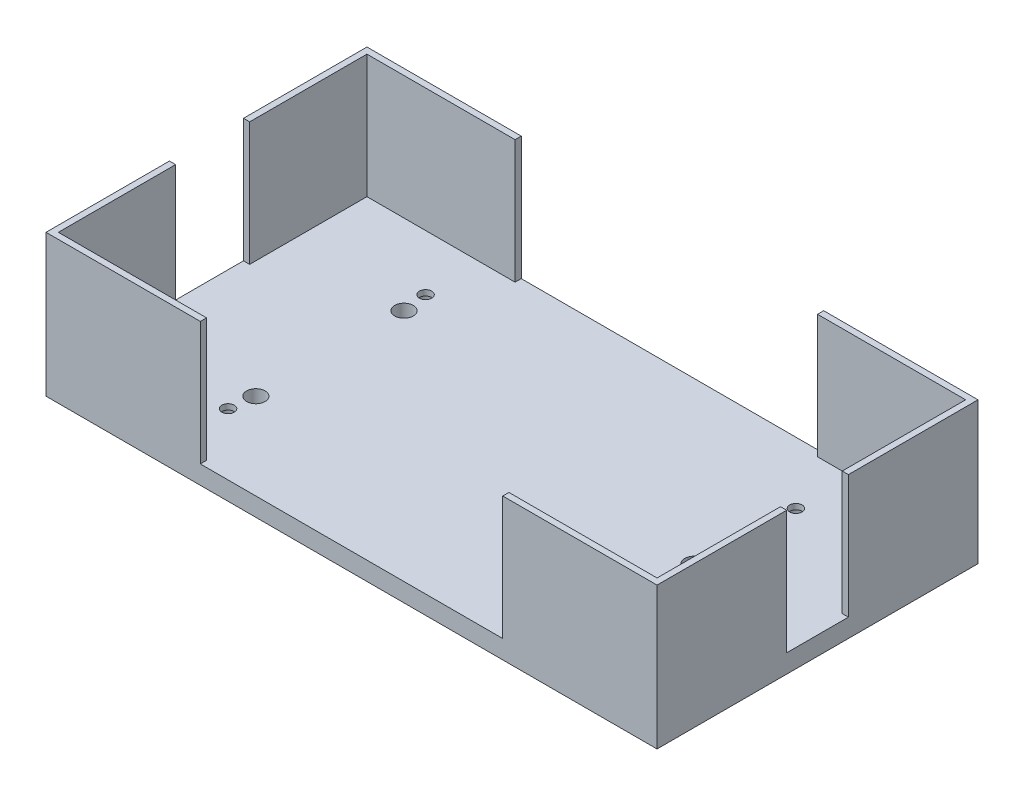
SolidWorks part; units mm, degrees
ref_plane "Front Plane" through (0, 0, 0) normal (0, 0, 1) x (1, 0, 0)
ref_plane "Top Plane" through (0, 0, 0) normal (0, 1, 0) x (1, 0, 0)
ref_plane "Right Plane" through (0, 0, 0) normal (1, 0, 0) x (0, 0, -1)
sketch "Sketch1" plane through (0, 0, 0) normal (0, 1, 0) x (1, 0, 0)
  line L1 (-60.2291, 12.7329) -> (38.7709, 12.7329)
  line L2 (-60.2291, 12.7329) -> (-60.2291, -39.2671)
  line L3 (-60.2291, -39.2671) -> (38.7709, -39.2671)
  line L4 (38.7709, 12.7329) -> (38.7709, -39.2671)
  dimension "D1" = 52
  dimension "D2" = 99
extrude "Boss-Extrude1" add sketch "Sketch1" along normal blind 3 contours L2 L1 L4 L3
sketch "Sketch5" plane through (0, 3, 0) normal (0, 1, 0) x (1, 0, 0)
  line L0 (-60.2291, 12.7329) -> (-60.2291, -39.2671) construction
  line L1 (-60.2291, -39.2671) -> (38.7709, -39.2671) construction
  line L3 (38.7709, 12.7329) -> (38.7709, -39.2671) construction
  circle A0 centre (-40.2291, -25.2671) radius 1.5
  circle A1 centre (-40.2291, -1.2671) radius 1.5
  circle A2 centre (18.7709, -13.2671) radius 1.5
  dimension "D1" = 3
  dimension "D2" = 3
  dimension "D3" = 3
  dimension "D4" = 20
  dimension "D5" = 14
  dimension "D6" = 20
  dimension "D7" = 24
  dimension "D8" = 26
  dimension "D9" = 20
extrude "Cut-Extrude3" cut sketch "Sketch5" against normal through all
sketch "Sketch6" plane through (0, 3, 0) normal (0, 1, 0) x (1, 0, 0)
  line L0 (-60.2291, 12.7329) -> (-60.2291, -39.2671) construction
  line L1 (-60.2291, -38.2671) -> (-59.2291, -38.2671)
  line L2 (-60.2291, -38.2671) -> (-60.2291, -19.2671)
  line L3 (-60.2291, -19.2671) -> (-59.2291, -19.2671)
  line L4 (-59.2291, -38.2671) -> (-59.2291, -19.2671)
  line L5 (-60.2291, -39.2671) -> (38.7709, -39.2671) construction
  line L6 (-60.2291, -7.2671) -> (-59.2291, -7.2671)
  line L7 (-60.2291, -7.2671) -> (-60.2291, 11.7329)
  line L8 (-60.2291, 11.7329) -> (-59.2291, 11.7329)
  line L9 (-59.2291, -7.2671) -> (-59.2291, 11.7329)
  line L10 (-60.2291, 12.7329) -> (38.7709, 12.7329) construction
  line L11 (38.7709, 12.7329) -> (38.7709, -39.2671) construction
  line L12 (37.7709, -38.2671) -> (38.7709, -38.2671)
  line L13 (37.7709, -38.2671) -> (37.7709, -18.2671)
  line L14 (37.7709, -18.2671) -> (38.7709, -18.2671)
  line L15 (38.7709, -38.2671) -> (38.7709, -18.2671)
  line L17 (37.7709, -8.2671) -> (38.7709, -8.2671)
  line L18 (37.7709, -8.2671) -> (37.7709, 11.7329)
  line L19 (37.7709, 11.7329) -> (38.7709, 11.7329)
  line L20 (38.7709, -8.2671) -> (38.7709, 11.7329)
  line L21 (-60.2291, -39.2671) -> (-35.2291, -39.2671)
  line L22 (-60.2291, -39.2671) -> (-60.2291, -38.2671)
  line L23 (-60.2291, -38.2671) -> (-35.2291, -38.2671)
  line L24 (-35.2291, -39.2671) -> (-35.2291, -38.2671)
  line L25 (13.7709, -39.2671) -> (38.7709, -39.2671)
  line L26 (13.7709, -39.2671) -> (13.7709, -38.2671)
  line L27 (13.7709, -38.2671) -> (38.7709, -38.2671)
  line L28 (38.7709, -39.2671) -> (38.7709, -38.2671)
  line L29 (-60.2291, 11.7329) -> (-35.2291, 11.7329)
  line L30 (-60.2291, 11.7329) -> (-60.2291, 12.7329)
  line L31 (-60.2291, 12.7329) -> (-35.2291, 12.7329)
  line L32 (-35.2291, 11.7329) -> (-35.2291, 12.7329)
  line L33 (13.7709, 11.7329) -> (38.7709, 11.7329)
  line L34 (13.7709, 11.7329) -> (13.7709, 12.7329)
  line L35 (13.7709, 12.7329) -> (38.7709, 12.7329)
  line L36 (38.7709, 11.7329) -> (38.7709, 12.7329)
  point P20 (38.2709, -38.2671)
  point P41 (38.7709, 12.2329)
  line M33 (38.7709, -39.2671) -> (38.7709, 12.7329)
  line M34 (38.7709, 12.7329) -> (-60.2291, 12.7329)
  line M35 (-60.2291, 12.7329) -> (-60.2291, -39.2671)
  dimension "D1" = 19
  dimension "D2" = 1
  dimension "D3" = 0
  dimension "D4" = 1
  dimension "D5" = 0
  dimension "D6" = 1
  dimension "D7" = 12
  dimension "D8" = 1
  dimension "D9" = 20
  dimension "D10" = 1
  dimension "D11" = 0
  dimension "D12" = 1
  dimension "D13" = 20
  dimension "D14" = 1
  dimension "D15" = 0
  dimension "D16" = 1
  dimension "D17" = 25
  dimension "D18" = 0
  dimension "D19" = 0
  dimension "D20" = 1
  dimension "D21" = 25
  dimension "D22" = 1
  dimension "D23" = 0
  dimension "D24" = 0
  dimension "D25" = 25
  dimension "D26" = 0
  dimension "D27" = 0
  dimension "D28" = 1
  dimension "D29" = 25
  dimension "D30" = 1
  dimension "D31" = 0
  dimension "D32" = 0
extrude "Boss-Extrude3" add sketch "Sketch6" along normal blind 20 contours L1 L4 L3 M35 | L34 L33 L19 M33 M34 | L22 L21 L24 L23 | L7 L8 L9 L6 | L31 L32 L29 L30 | L18 L19 L20 L17 | L25 L28 L27 L26 | L13 L14 L15 L12 region at (-59.7291, 3, 28.7671) region at (26.2709, 3, -12.2329)
sketch "Sketch7" plane through (0, 3, 0) normal (0, 1, 0) x (1, 0, 0)
  line L0 (-60.2291, -7.2671) -> (-60.2291, -19.2671) construction
  line L1 (-35.2291, -39.2671) -> (13.7709, -39.2671) construction
  circle A0 centre (19.2709, -29.2671) radius 1
  circle A1 centre (-40.7291, -29.2671) radius 1
  circle A2 centre (19.2709, 2.7329) radius 1
  circle A3 centre (-40.7291, 2.7329) radius 1
  dimension "D1" = 2
  dimension "D2" = 2
  dimension "D3" = 2
  dimension "D4" = 2
  dimension "D5" = 32
  dimension "D6" = 60
  dimension "D7" = 60
  dimension "D8" = 32
  dimension "D9" = 19.5
  dimension "D10" = 19.5
  dimension "D11" = 10
  dimension "D12" = 10
extrude "Cut-Extrude4" cut sketch "Sketch7" against normal through all
sketch "Sketch8" plane through (0, 0, 0) normal (0, -1, 0) x (-1, 0, 0)
  circle A0 centre (-19.2709, -29.2671) radius 1.85
  circle A1 centre (-19.2709, 2.7329) radius 1.85
  circle A2 centre (40.7291, -29.2671) radius 1.85
  circle A3 centre (40.7291, 2.7329) radius 1.85
  circle A4 centre (-19.2709, -29.2671) radius 1 construction
  circle A5 centre (-19.2709, 2.7329) radius 1 construction
  circle A7 centre (40.7291, -29.2671) radius 1 construction
  circle A8 centre (40.7291, 2.7329) radius 1 construction
  point P10 (0, 0)
  dimension "D1" = 3.7
  dimension "D2" = 3.7
  dimension "D3" = 3.7
  dimension "D4" = 3.7
  dimension "D5" = 0
  dimension "D6" = 0
extrude "Cut-Extrude5" cut sketch "Sketch8" against normal blind 2.1
